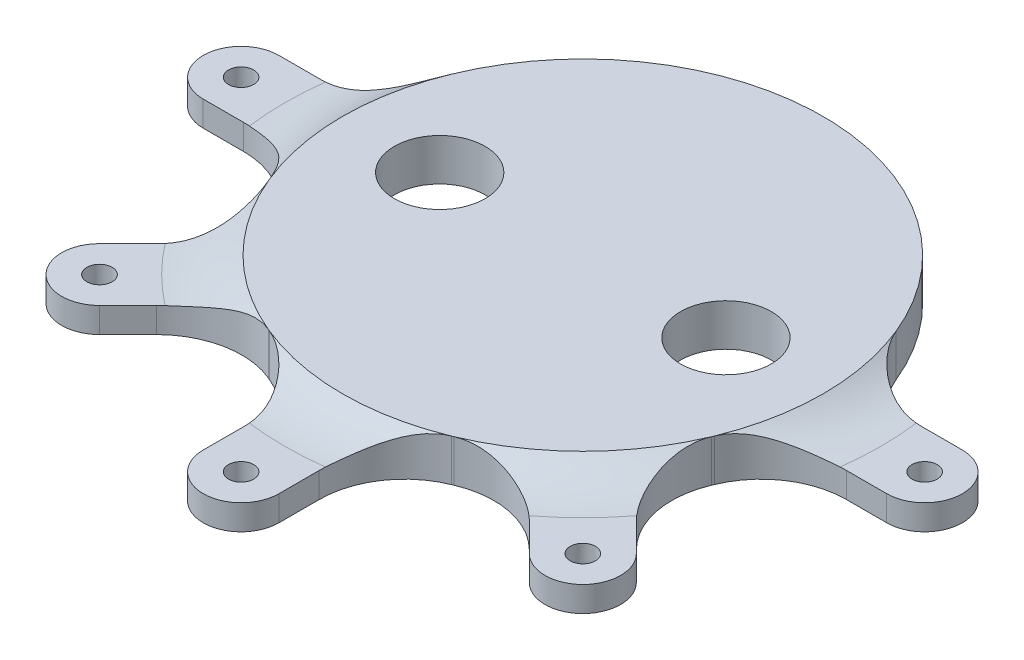
SolidWorks part; units mm, degrees
ref_plane "Front Plane" through (0, 0, 0) normal (0, 0, 1) x (1, 0, 0)
ref_plane "Top Plane" through (0, 0, 0) normal (0, 1, 0) x (1, 0, 0)
ref_plane "Right Plane" through (0, 0, 0) normal (1, 0, 0) x (0, 0, -1)
sketch "Sketch1" plane through (0, 0, 0) normal (0, 1, 0) x (1, 0, 0)
  line L0 (0, 28.575) -> (0, -28.575) construction
  circle A0 centre (0, 0) radius 28.575
  circle A1 centre (-17.018, 0) radius 5.3975
  circle A2 centre (17.018, 0) radius 5.3975
  point P9 (0, 0)
  dimension "D1" = 57.15
  dimension "D3" = 10.795
  dimension "D2" = 34.036
extrude "Boss-Extrude1" add sketch "Sketch1" along normal blind 5 contours L0 A0 A1 | A0 L0 A2 region at (19.7538, 0, -19.7538) region at (-0.639, 0, 0)
sketch "Sketch2" plane through (0, 0, 0) normal (0, 1, 0) x (1, 0, 0)
  line L0 (0, 28.575) -> (0, -28.575) construction
  line L3 (4.5, -40.64) -> (4.5, -28.2184)
  line L4 (-4.5, -40.64) -> (-4.5, -28.2184)
  line L9 (-25.5548, -31.9188) -> (-16.7715, -23.1354)
  line L10 (-31.9188, -25.5548) -> (-23.1354, -16.7715)
  line L11 (-40.64, -4.5) -> (-28.2184, -4.5)
  line L12 (-40.64, 4.5) -> (-28.2184, 4.5)
  line L13 (31.9188, -25.5548) -> (23.1354, -16.7715)
  line L14 (25.5548, -31.9188) -> (16.7715, -23.1354)
  line L15 (40.64, 4.5) -> (28.2184, 4.5)
  line L16 (40.64, -4.5) -> (28.2184, -4.5)
  circle A7 centre (0, 0) radius 28.575 construction
  circle A14 centre (0, 0) radius 40.64 construction
  circle A15 centre (0, -40.64) radius 1.5
  arc A16 (-4.5, -40.64) -> (4.5, -40.64) centre (0, -40.64) ccw
  arc A18 (-4.5, -28.2184) -> (4.5, -28.2184) centre (0, 0) ccw
  arc A20 (-4.5, -28.2184) -> (4.5, -28.2184) centre (0, 0) ccw
  circle A25 centre (-28.7368, -28.7368) radius 1.5
  arc A26 (-31.9188, -25.5548) -> (-25.5548, -31.9188) centre (-28.7368, -28.7368) ccw
  arc A27 (-23.1354, -16.7715) -> (-16.7715, -23.1354) centre (0, 0) ccw
  arc A28 (-23.1354, -16.7715) -> (-16.7715, -23.1354) centre (0, 0) ccw
  circle A29 centre (-40.64, 0) radius 1.5
  arc A30 (-40.64, 4.5) -> (-40.64, -4.5) centre (-40.64, 0) ccw
  arc A31 (-28.2184, 4.5) -> (-28.2184, -4.5) centre (0, 0) ccw
  arc A32 (-28.2184, 4.5) -> (-28.2184, -4.5) centre (0, 0) ccw
  circle A33 centre (28.7368, -28.7368) radius 1.5
  arc A34 (25.5548, -31.9188) -> (31.9188, -25.5548) centre (28.7368, -28.7368) ccw
  arc A35 (16.7715, -23.1354) -> (23.1354, -16.7715) centre (0, 0) ccw
  arc A36 (16.7715, -23.1354) -> (23.1354, -16.7715) centre (0, 0) ccw
  circle A37 centre (40.64, 0) radius 1.5
  arc A38 (40.64, -4.5) -> (40.64, 4.5) centre (40.64, 0) ccw
  arc A39 (28.2184, -4.5) -> (28.2184, 4.5) centre (0, 0) ccw
  arc A40 (28.2184, -4.5) -> (28.2184, 4.5) centre (0, 0) ccw
  point P5 (0, 0)
  point P12 (0, 0)
  point P26 (0, 0)
  point P40 (0, 0)
  dimension "D1" = 4.5
  dimension "D2" = 3
  dimension "D3" = 81.28
  dimension "D4" = 3
extrude "Boss-Extrude2" add sketch "Sketch2" along normal blind 3 contours A18 L4 A16 L3 A15 | A25 | A31 L12 A30 L11 A29 | A35 L14 A34 L13 A33 | A39 L16 A38 L15 A37 region at (0, 0, 36.1213) region at (-25.5416, 0, 25.5416) region at (-36.1213, 0, 0) region at (25.5416, 0, 25.5416) region at (36.1213, 0, 0)
fillet "Fillet1" radius 12.7 5 edges at (0, 3, 28.575) (-20.2056, 3, 20.2056) (28.575, 3, 0) (20.2056, 3, 20.2056) (-28.575, 3, 0)
fillet "Fillet2" radius 10.16 10 edges at (4.5, 2.5, 28.2184) (-4.5, 2.5, 28.2184) (28.2184, 2.5, -4.5) (28.2184, 2.5, 4.5) (23.1354, 2.5, 16.7715) (-28.2184, 2.5, -4.5) (-28.2184, 2.5, 4.5) (16.7715, 2.5, 23.1354) (-23.1354, 2.5, 16.7715) (-16.7715, 2.5, 23.1354)
sketch "Sketch4" plane through (0, 0, 0) normal (0, 1, 0) x (1, 0, 0)
  circle A0 centre (0, 0) radius 37.465
  circle A1 centre (0, 0) radius 40.64
  dimension "D1" = 74.93
